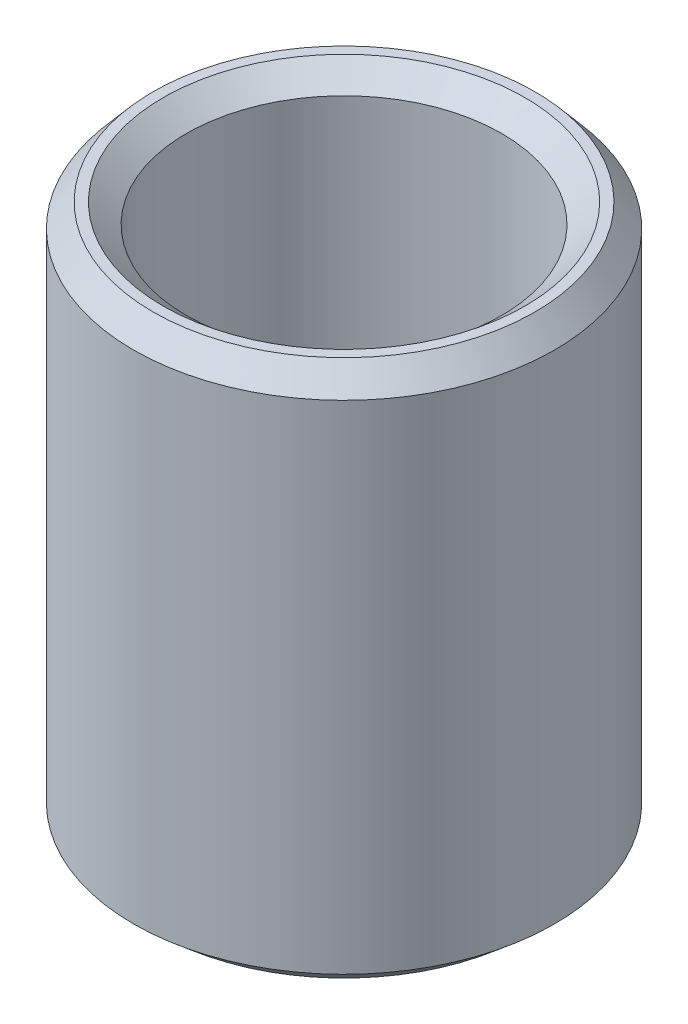
SolidWorks part; units mm, degrees
ref_plane "Front Plane" through (0, 0, 0) normal (0, 0, 1) x (1, 0, 0)
ref_plane "Top Plane" through (0, 0, 0) normal (0, 1, 0) x (1, 0, 0)
ref_plane "Right Plane" through (0, 0, 0) normal (1, 0, 0) x (0, 0, -1)
sketch "Sketch1" plane through (0, 0, 0) normal (0, 1, 0) x (1, 0, 0)
  circle A0 centre (0, 0) radius 10
  dimension "SLEEVE_OD" = 20
extrude "Boss-Extrude1" add sketch "Sketch1" along normal blind 25.6444
sketch "Sketch2" plane through (0, 0, 0) normal (0, 1, 0) x (1, 0, 0)
  circle A0 centre (0, 0) radius 7.4906
  dimension "BORE_D" = 14.9811
extrude "Cut-Extrude1" cut sketch "Sketch2" along normal through all
chamfer "Chamfer1" distance 1.0969 angle 40.344 4 edges at (0, 25.6444, 7.4906) (0, 0, 7.4906) (0, 0, 10) (0, 25.6444, 10) first distance on face at (0, 25.6444, 7.4906) first distance on face at (0, 0, 7.4906) first distance on face at (0, 25.6444, 10)
